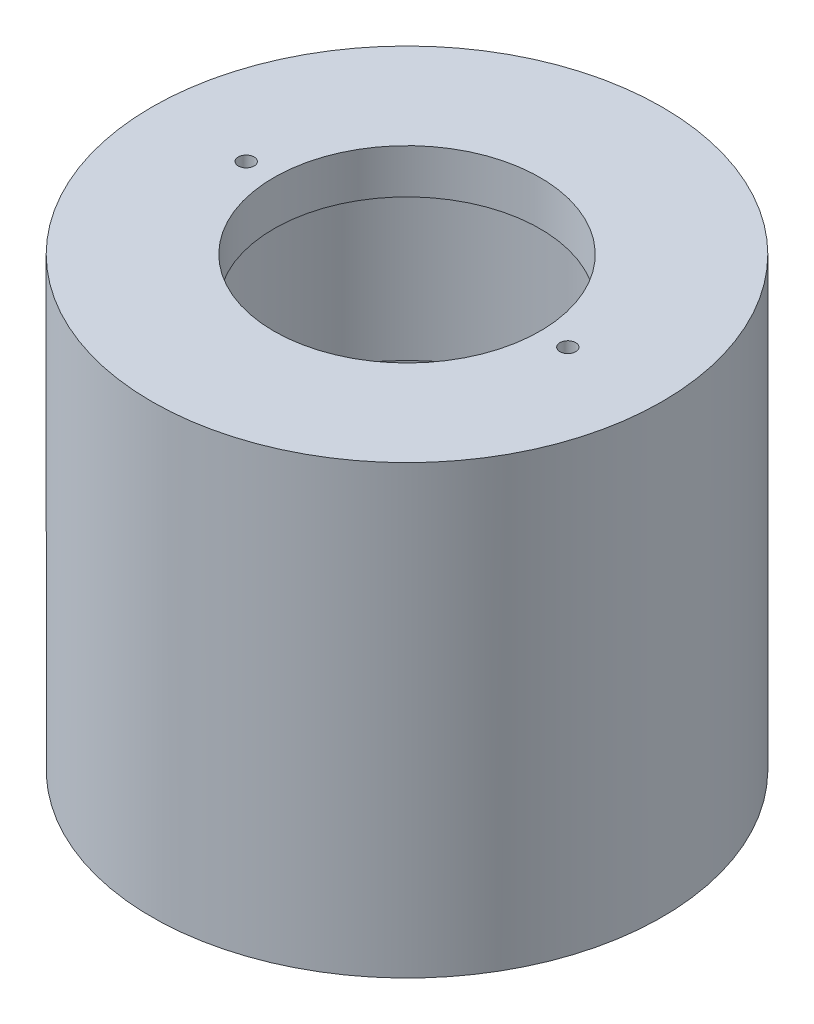
SolidWorks part; units mm, degrees
material "Delrin 2700 NC010, Low Viscosity Acetal Copolymer (SS)"
ref_plane "Front Plane" through (0, 0, 0) normal (0, 0, 1) x (1, 0, 0)
ref_plane "Top Plane" through (0, 0, 0) normal (0, 1, 0) x (1, 0, 0)
ref_plane "Right Plane" through (0, 0, 0) normal (1, 0, 0) x (0, 0, -1)
sketch "Sketch1" plane through (0, 0, 0) normal (0, 1, 0) x (1, 0, 0)
  circle A0 centre (0, 0) radius 33.3375
  circle A1 centre (0, 0) radius 36.5125
  dimension "D1" = 66.675
  dimension "D2" = 3.175
extrude "Boss-Extrude1" add sketch "Sketch1" along normal blind 51.435
sketch "Sketch6" plane through (0, 0, 0) normal (0, -1, 0) x (1, 0, 0)
  circle A2 centre (0, 0) radius 33.3375
  circle A3 centre (0, 0) radius 33.3375
  circle A5 centre (0, 0) radius 36.5125
  circle A6 centre (0, 0) radius 36.5125
  dimension "D1" = 0
  dimension "D2" = 0
extrude "Boss-Extrude5" add sketch "Sketch6" along normal blind 6.096
ref_plane "Plane2" through (0, 23.114, 0) normal (0, -1, 0) x (1, 0, 0)
sketch "Sketch12" plane through (0, 23.114, 0) normal (0, -1, 0) x (1, 0, 0)
  circle A0 centre (0, 0) radius 25.4
  circle A5 centre (0, 0) radius 33.3375
  dimension "D1" = 50.8
  dimension "D2" = 66.675
extrude "Boss-Extrude8" add sketch "Sketch12" against normal up to surface (28.321 mm away) up to face at (0, 51.435, 36.5125)
sketch "Sketch2" plane through (0, 51.435, 0) normal (0, 1, 0) x (1, 0, 0)
  circle A0 centre (0, 0) radius 19.05
  circle A3 centre (0, 0) radius 36.5125
  circle A4 centre (0, 0) radius 36.5125
  dimension "D1" = 38.1
  dimension "D2" = 0
extrude "Boss-Extrude2" add sketch "Sketch2" along normal blind 6.35
ref_plane "Plane1" through (0, 26.67, 0) normal (0, -1, 0) x (1, 0, 0)
sketch "Sketch4" plane through (0, 26.67, 0) normal (0, -1, 0) x (1, 0, 0)
  circle A0 centre (0, 0) radius 26.9494
  dimension "D1" = 53.8988
extrude "Cut-Extrude1" cut sketch "Sketch4" along normal blind 1.7272
sketch "Sketch5" plane through (0, 57.785, 0) normal (0, 1, 0) x (1, 0, 0)
  line L0 (0, 0) -> (0, 12.0132) construction
  circle A0 centre (-23.0124, 0) radius 1.1303
  circle A1 centre (23.0124, 0) radius 1.1303
  dimension "D1" = 2.2606
  dimension "D2" = 46.0248
  dimension "D3" = 23.0124
extrude "Cut-Extrude5" cut sketch "Sketch5" against normal through all
cosmetic thread "Cosmetic Thread1" parameters "D2"=2.8448
cosmetic thread "Cosmetic Thread2" parameters "D2"=2.8448
